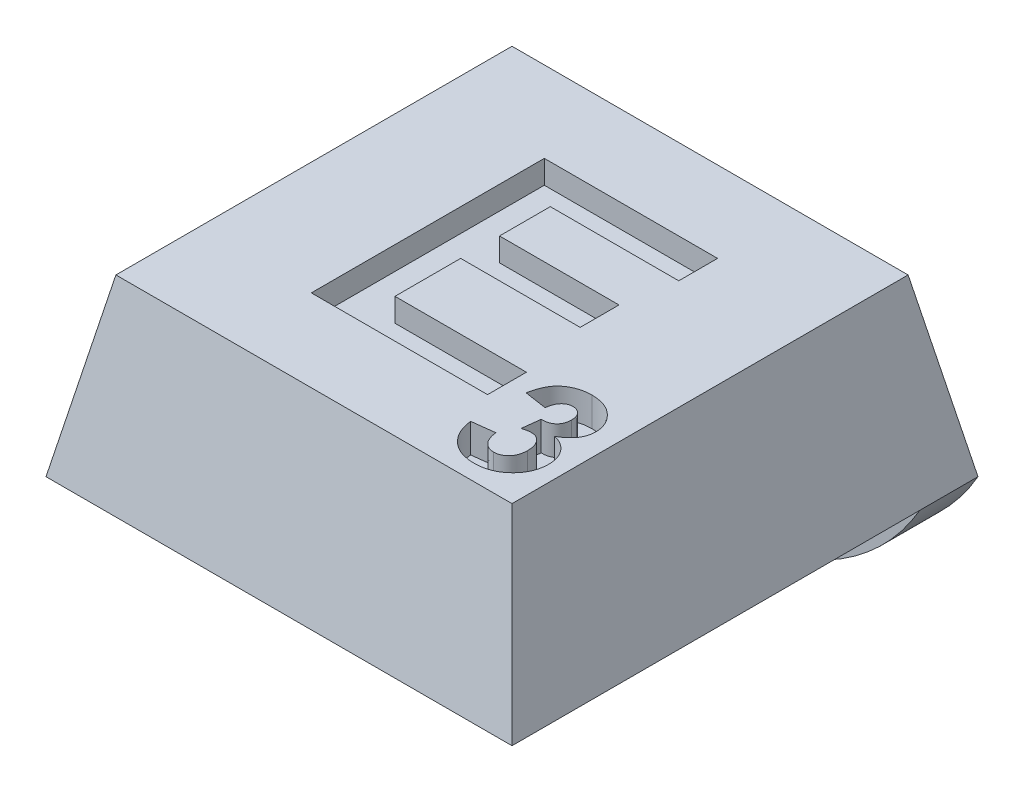
SolidWorks part; units mm, degrees
ref_plane "Front Plane" through (0, 0, 0) normal (0, 0, 1) x (1, 0, 0)
ref_plane "Top Plane" through (0, 0, 0) normal (0, 1, 0) x (1, 0, 0)
ref_plane "Right Plane" through (0, 0, 0) normal (1, 0, 0) x (0, 0, -1)
sketch "Sketch1" plane through (0, 0, 0) normal (0, 1, 0) x (1, 0, 0)
  line L1 (0, 0) -> (8, 0)
  line L2 (0, 0) -> (0, 8)
  line L3 (0, 8) -> (8, 8)
  line L4 (8, 0) -> (8, 8)
  dimension "D1" = 8
  dimension "D2" = 8
extrude "Boss-Extrude1" add sketch "Sketch1" along normal blind 3
sketch "Sketch2" plane through (0, 0, 0) normal (0, 0, 1) x (1, 0, 0)
  line L0 (0, 0) -> (0.6, 3)
  line L1 (0, 3) -> (8, 3) construction
  line L2 (0.6, 3) -> (0, 3)
  line L3 (0, 3) -> (0, 0)
  line L4 (8, 0) -> (7.4, 3)
  line L5 (7.4, 3) -> (8, 3)
  line L6 (8, 3) -> (8, 0)
  dimension "D1" = 0.6
  dimension "D2" = 0.6
extrude "Cut-Extrude1" cut sketch "Sketch2" against normal through all both and the other way through all
sketch "Sketch3" plane through (0, 0, 0) normal (1, 0, 0) x (0, 0, -1)
  line L0 (0, 0) -> (0.6, 3)
  line L1 (8, 3) -> (0, 3) construction
  line L2 (0.6, 3) -> (0, 3)
  line L3 (0, 3) -> (0, 0)
  line L4 (8, 3) -> (7.4, 3)
  line L5 (7.4, 3) -> (8, 0)
  line L6 (8, 3) -> (8, 0)
  dimension "D1" = 0.6
  dimension "D2" = 0.6
extrude "Cut-Extrude2" cut sketch "Sketch3" along normal blind 11
sketch "Sketch4" plane through (0, 0, 0) normal (0, -1, 0) x (1, 0, 0)
  line L0 (8, 0) -> (8, -8) construction
  line L3 (0, 0) -> (8, 0) construction
  circle A0 centre (4, -3.75) radius 1.75
  dimension "D1" = 3.5
  dimension "D2" = 4
  dimension "D3" = 3.75
extrude "Cut-Extrude3" cut sketch "Sketch4" against normal blind 0.4
sketch "Sketch5" plane through (0, 0, 0) normal (0, -1, 0) x (1, 0, 0)
  line L0 (8, 0) -> (8, -8) construction
  line L1 (0, -8) -> (8, -8)
  line L2 (0, -8) -> (0, -7)
  line L3 (0, -7) -> (8, -7)
  line L4 (8, -8) -> (8, -7)
  dimension "D1" = 1
extrude "Boss-Extrude2" add sketch "Sketch5" along normal blind 2
fillet "Fillet1" radius 4 2 edges at (8, -2, -7.5) (0, -2, -7.5)
sketch "Sketch6" plane through (0, 3, 0) normal (0, 1, 0) x (1, 0, 0)
  text T0 "E" font "Arial" height 4
extrude "Cut-Extrude4" cut sketch "Sketch6" against normal blind 0.4
sketch "Sketch7" plane through (0, 3, 0) normal (0, 1, 0) x (1, 0, 0)
  text T0 "3" font "Arial" height 2
extrude "Cut-Extrude5" cut sketch "Sketch7" against normal blind 0.5
